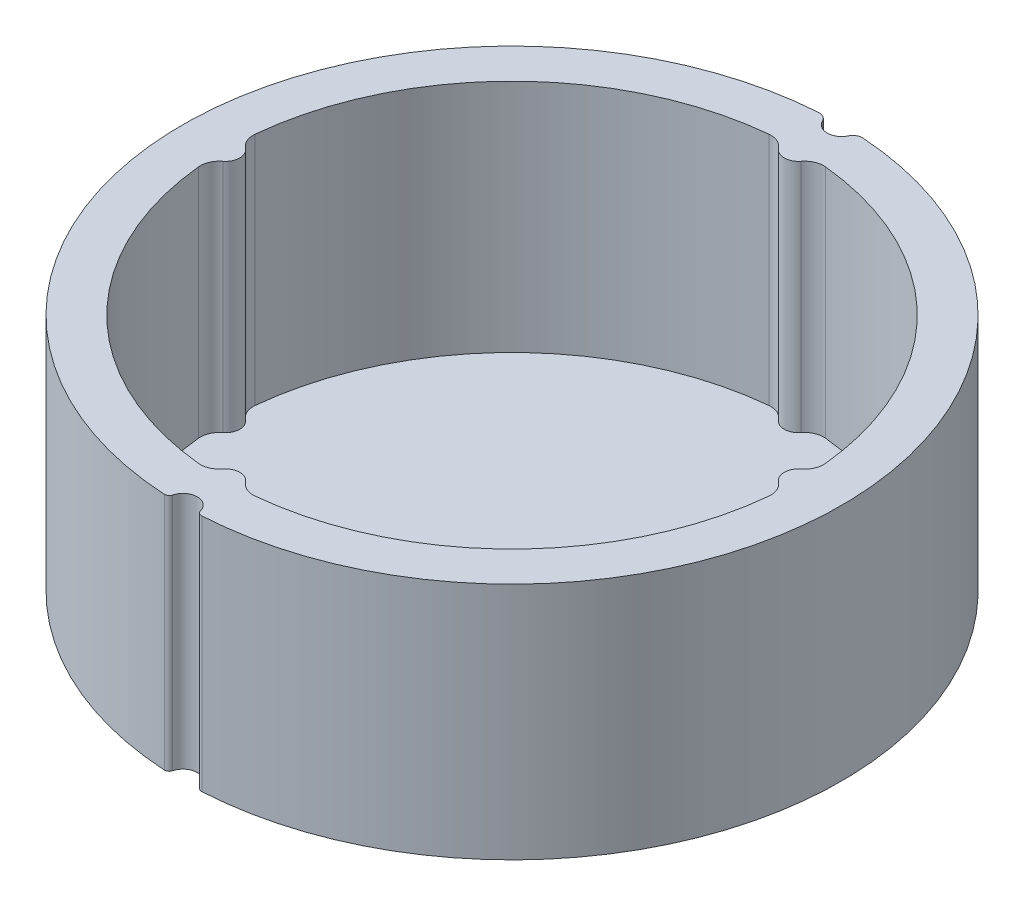
SolidWorks part; units mm, degrees
ref_plane "Front Plane" through (0, 0, 0) normal (0, 0, 1) x (1, 0, 0)
ref_plane "Top Plane" through (0, 0, 0) normal (0, 1, 0) x (1, 0, 0)
ref_plane "Right Plane" through (0, 0, 0) normal (1, 0, 0) x (0, 0, -1)
sketch "Sketch1" plane through (0, 0, 0) normal (0, 1, 0) x (1, 0, 0)
  line L3 (0, 0.002) -> (0, 3.7877) construction
  line L4 (0, 3.7877) -> (2.417, 3.7877)
  line L5 (0, 3.7877) -> (-2.417, 3.7877)
  arc A0 (1.9642, -34.442) -> (34.1982, 4.5552) centre (0, 0.002) ccw
  arc A2 (-2.417, 3.7877) -> (2.417, 3.7877) centre (0, 0.002) ccw
  circle A3 centre (0, 0.002) radius 34.5 construction
  arc A7 (-1.3541, 33.8562) -> (1.3541, 33.8562) centre (0, 34.5015) ccw
  arc A8 (34.1982, 4.5552) -> (2.3241, 34.4236) centre (0, 0.002) ccw
  arc A9 (-2.3241, 34.4236) -> (-34.1982, 4.5552) centre (0, 0.002) ccw
  arc A10 (-34.1982, 4.5552) -> (-1.9642, -34.442) centre (0, 0.002) ccw
  arc A11 (1.3541, 33.8562) -> (2.3241, 34.4236) centre (2.2568, 33.4259) cw
  arc A12 (-1.3541, 33.8562) -> (-2.3241, 34.4236) centre (-2.2568, 33.4259) ccw
  arc A13 (1.4518, -34.0686) -> (-1.4518, -34.0686) centre (0, -34.4457) ccw
  arc A14 (1.4518, -34.0686) -> (1.9642, -34.442) centre (1.9358, -33.9428) ccw
  arc A15 (-1.4518, -34.0686) -> (-1.9642, -34.442) centre (-1.9358, -33.9428) cw
  point P15 (1.4997, 34.4694)
  dimension "D2" = 4.834
  dimension "D3" = 4.4915
  dimension "D4" = 34.5
  dimension "D5" = 1
  dimension "D6" = 1.5
  dimension "D7" = 0.5
  dimension "D11" = 1.4997
sketch "Sketch2" plane through (0, 0, 0) normal (0, 1, 0) x (1, 0, 0)
  arc A0 (-29.8527, -2.9694) -> (-2.9694, -29.8527) centre (0, 0) ccw
  arc A1 (-1.1878, 29.0839) -> (1.1878, 29.0839) centre (0, 30) ccw
  arc A2 (29.0839, 1.1878) -> (29.0839, -1.1878) centre (30, 0) ccw
  arc A3 (1.1878, -29.0839) -> (-1.1878, -29.0839) centre (0, -30) ccw
  arc A4 (-29.0839, -1.1878) -> (-29.0839, 1.1878) centre (-30, 0) ccw
  arc A5 (-2.9694, 29.8527) -> (-29.8527, 2.9694) centre (0, 0) ccw
  arc A6 (29.8527, 2.9694) -> (2.9694, 29.8527) centre (0, 0) ccw
  arc A7 (2.9694, -29.8527) -> (29.8527, -2.9694) centre (0, 0) ccw
  arc A8 (-29.0839, -1.1878) -> (-29.8527, -2.9694) centre (-27.8625, -2.7715) ccw
  arc A9 (-29.0839, 1.1878) -> (-29.8527, 2.9694) centre (-27.8625, 2.7715) cw
  arc A10 (1.1878, -29.0839) -> (2.9694, -29.8527) centre (2.7715, -27.8625) ccw
  arc A11 (-1.1878, -29.0839) -> (-2.9694, -29.8527) centre (-2.7715, -27.8625) cw
  arc A12 (29.0839, 1.1878) -> (29.8527, 2.9694) centre (27.8625, 2.7715) ccw
  arc A13 (29.0839, -1.1878) -> (29.8527, -2.9694) centre (27.8625, -2.7715) cw
  arc A14 (1.1878, 29.0839) -> (2.9694, 29.8527) centre (2.7715, 27.8625) cw
  arc A15 (-1.1878, 29.0839) -> (-2.9694, 29.8527) centre (-2.7715, 27.8625) ccw
  point P21 (1.4995, -29.9625)
  point P26 (29.9625, 1.4995)
  point P33 (-1.4995, 29.9625)
  dimension "D1" = 30
  dimension "D2" = 1.5
  dimension "D3" = 1.5
  dimension "D4" = 1.5
  dimension "D5" = 1.5
  dimension "D6" = 2
extrude "Boss-Extrude1" add sketch "Sketch1" along normal blind 25 contours A10 A0 A8 A7 A9 A2 L5 L4 region at (2.2155, 0, 33.5591)
extrude "Cut-Extrude2" cut sketch "Sketch2" along normal through all
extrude "Boss-Extrude2" add sketch "Sketch2<2>" along normal blind 0.4
sketch "Sketch2<2>" plane through (0, 0, 0) normal (0, 1, 0) x (1, 0, 0) same geometry as "Sketch2"
